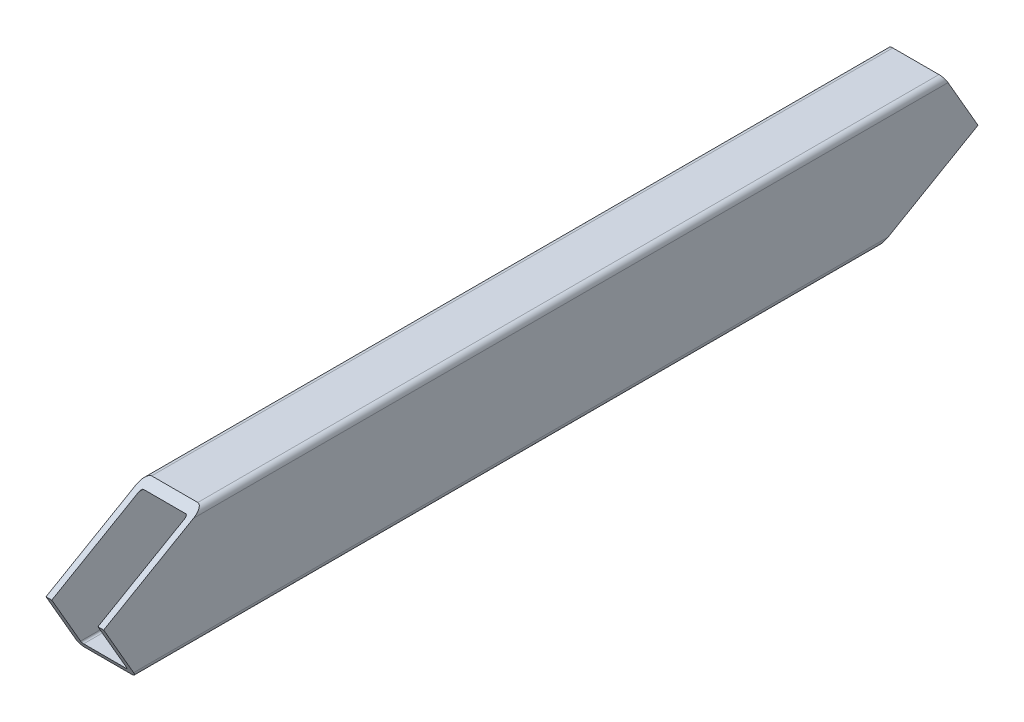
SolidWorks part; units mm, degrees
ref_plane "Płaszczyzna przednia" through (0, 0, 0) normal (0, 0, 1) x (1, 0, 0)
ref_plane "Płaszczyzna górna" through (0, 0, 0) normal (0, 1, 0) x (1, 0, 0)
ref_plane "Płaszczyzna prawa" through (0, 0, 0) normal (1, 0, 0) x (0, 0, -1)
sketch "Szkic1" plane through (0, 0, 0) normal (0, 0, 1) x (1, 0, 0)
  line L0 (-11, -3) -> (11, -3)
  line L1 (-12, -60) -> (12, -60)
  line L2 (-15, -57) -> (-15, -3)
  line L3 (-12, 0) -> (12, 0)
  line L4 (15, -57) -> (15, -3)
  line L5 (12, -56) -> (12, -4)
  line L6 (-11, -57) -> (11, -57)
  line L7 (-12, -56) -> (-12, -4)
  line L8 (-15, 0) -> (15, 0) construction
  line L9 (15, -60) -> (15, 0) construction
  line L10 (-15, -60) -> (15, -60) construction
  line L11 (-15, -60) -> (-15, 0) construction
  line L12 (-12, -3) -> (12, -3) construction
  line L13 (12, -57) -> (12, -3) construction
  line L14 (-12, -57) -> (12, -57) construction
  line L15 (-12, -57) -> (-12, -3) construction
  arc A0 (12, 0) -> (15, -3) centre (12, -3) cw
  arc A1 (15, -57) -> (12, -60) centre (12, -57) cw
  arc A2 (-12, -60) -> (-15, -57) centre (-12, -57) cw
  arc A3 (-15, -3) -> (-12, 0) centre (-12, -3) cw
  arc A4 (11, -3) -> (12, -4) centre (11, -4) cw
  arc A5 (12, -56) -> (11, -57) centre (11, -56) cw
  arc A6 (-11, -57) -> (-12, -56) centre (-11, -56) cw
  arc A7 (-12, -4) -> (-11, -3) centre (-11, -4) cw
  point P12 (15, 0)
  point P34 (0, 0)
  dimension "D4" = 3
  dimension "D1" = 1
  dimension "D2" = 30
  dimension "D5" = 60
  dimension "D3" = 3
extrude "Dodanie-wyciągnięcie1" add sketch "Szkic1" against normal blind 465
sketch "Szkic2" plane through (15, 0, 0) normal (1, 0, 0) x (0, 0, -1)
  line L0 (57.9615, 0) -> (6, -30)
  line L1 (465, 0) -> (0, 0) construction
  line L2 (465, -60) -> (0, -60) construction
  line L3 (0, -60) -> (0, 0)
  line L4 (0, 0) -> (57.9615, 0)
  line L5 (465, -60) -> (465, 0)
  line L6 (460.923, -30) -> (408.9615, -60)
  line L7 (408.9615, -60) -> (465, -60)
  line L8 (460.923, -30) -> (443.6025, 0)
  line L11 (443.6025, 0) -> (465, 0)
  line L12 (6, -30) -> (23.3205, -60)
  line L13 (23.3205, -60) -> (0, -60)
  dimension "D1" = 30
  dimension "D2" = 30
  dimension "D3" = 60
  dimension "D4" = 60
  dimension "D5" = 351
  dimension "D6" = 6
extrude "Wytnij-wyciągnięcie1" cut sketch "Szkic2" against normal up to surface (30 mm away) up to face at (-15, -30, -232.5)
